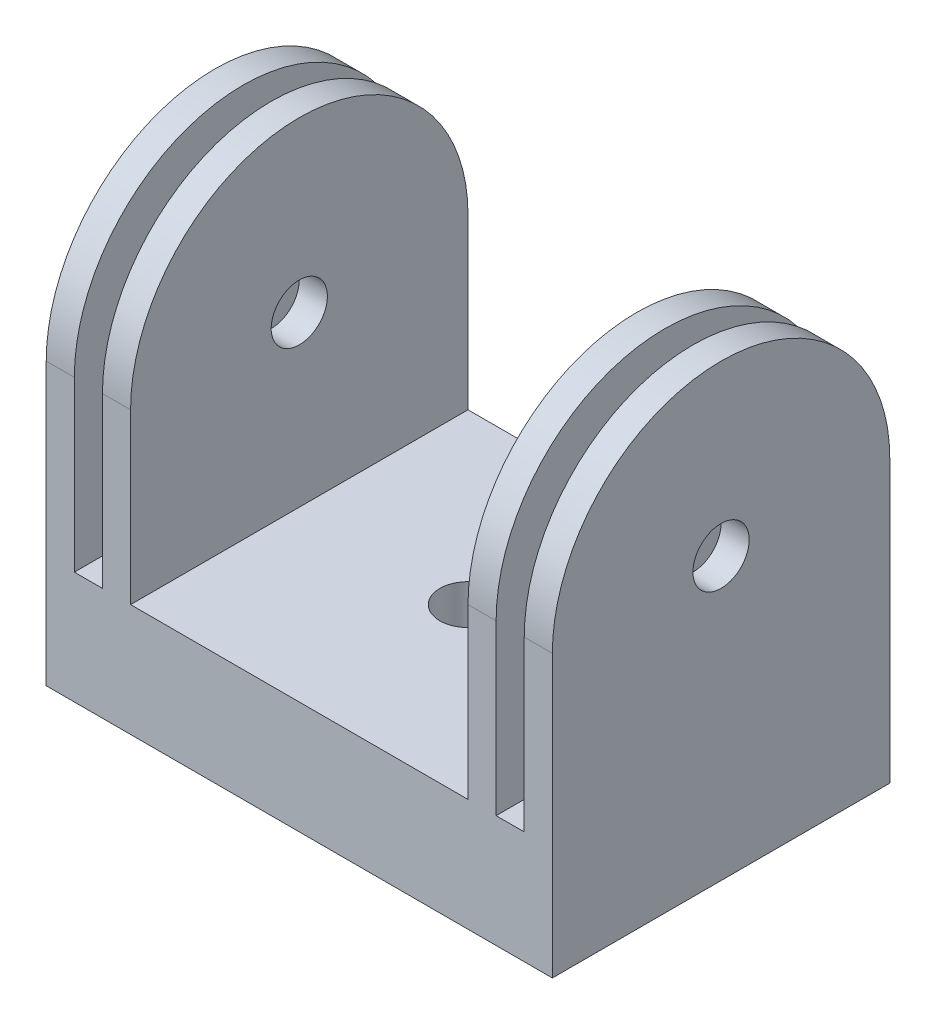
SolidWorks part; units mm, degrees
material "PET"
ref_plane "Front Plane" through (0, 0, 0) normal (0, 0, 1) x (1, 0, 0)
ref_plane "Top Plane" through (0, 0, 0) normal (0, 1, 0) x (1, 0, 0)
ref_plane "Right Plane" through (0, 0, 0) normal (1, 0, 0) x (0, 0, -1)
sketch "Sketch1" plane through (0, 0, 0) normal (0, 1, 0) x (1, 0, 0)
  line L1 (-22.5, 15) -> (22.5, 15)
  line L2 (-22.5, 15) -> (-22.5, -15)
  line L3 (-22.5, -15) -> (22.5, -15)
  line L4 (22.5, 15) -> (22.5, -15)
  line L5 (0, -15) -> (0, 15) construction
  line L6 (-22.5, 0) -> (22.5, 0) construction
  point P0 (0, 0)
  dimension "D1" = 45
  dimension "D2" = 30
extrude "Boss-Extrude1" add sketch "Sketch1" along normal blind 10 contours L4 L1 L2 L3
sketch "Sketch2" plane through (22.5, 0, 0) normal (1, 0, 0) x (0, 0, -1)
  line L0 (15, 10) -> (15, 0) construction
  line L1 (-15, 10) -> (15, 10)
  line L2 (-15, 10) -> (-15, 25)
  line L4 (15, 10) -> (15, 25)
  arc A0 (-15, 25) -> (15, 25) centre (0, 25) cw
  circle A1 centre (0, 25) radius 2.5
  dimension "D2" = 5
  dimension "D4" = 15
  dimension "D1" = 15
  dimension "D3" = 10
extrude "Boss-Extrude2" add sketch "Sketch2" against normal blind 2.5
ref_plane "Plane1" through (18.75, 0, 0) normal (1, 0, 0) x (0, 0, -1)
mirror "Mirror2" about plane through (18.75, 0, 0) normal (1, 0, 0) of "Boss-Extrude2"
mirror "Mirror3" about plane through (0, 0, 0) normal (1, 0, 0) of "Mirror2"
hole_wizard "M6x1.0 Tapped Hole1" positions "Sketch3" profile "Sketch4" tap size "M6x1.0" standard "ANSI Metric" end condition through all
sketch "Sketch3" plane through (0, 0, 0) normal (0, -1, 0) x (-1, 0, 0)
  line L0 (22.5, 0) -> (-22.5, 0) construction
  line L1 (22.5, 15) -> (22.5, -15) construction
  line L2 (-22.5, 15) -> (-22.5, -15) construction
  point P7 (0, 0)
sketch "Sketch4" plane through (0, 0, 0) normal (1, 0, 0) x (0, 0, -1)
  line L0 (0, 0) -> (0, 40)
  line L1 (0, 40) -> (2.5, 40)
  line L2 (2.5, 40) -> (2.5, 0)
  line L5 (2.5, 0) -> (0, 0)
  line L11 (0, -6.35) -> (0, 107.95) construction
  dimension "Thru Tap Drill Dia." = 5
  dimension "Thru Tap Drill Depth" = 40
cosmetic thread "Hole Thread1" parameters "D2"=6
